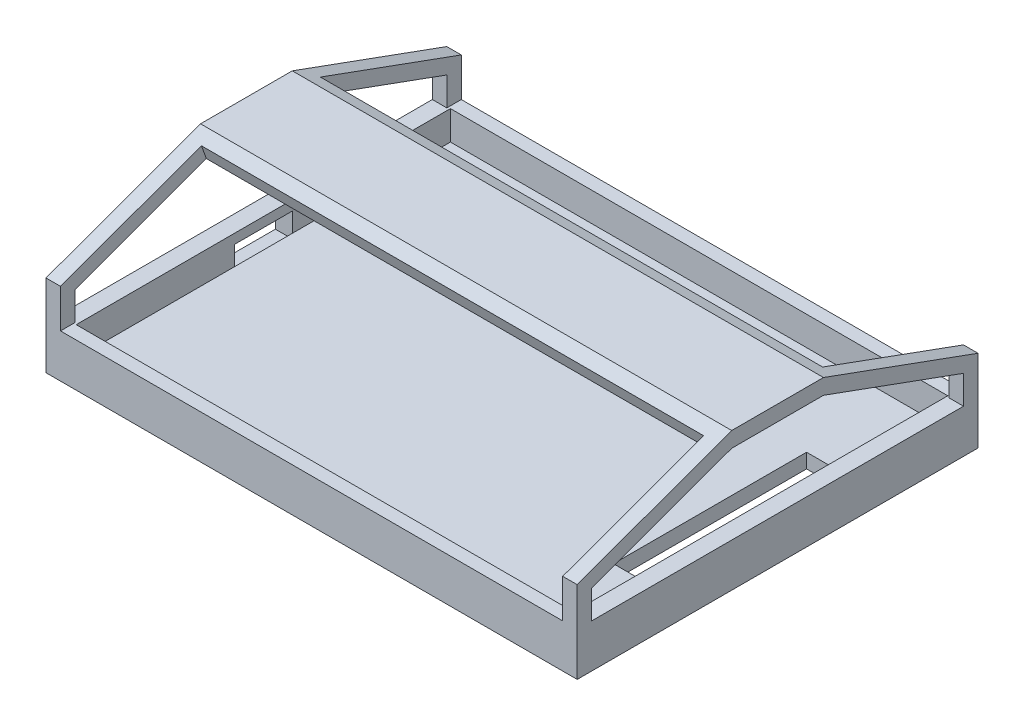
SolidWorks part; units mm, degrees
ref_plane "Front Plane" through (0, 0, 0) normal (0, 0, 1) x (1, 0, 0)
ref_plane "Top Plane" through (0, 0, 0) normal (0, 1, 0) x (1, 0, 0)
ref_plane "Right Plane" through (0, 0, 0) normal (1, 0, 0) x (0, 0, -1)
sketch "Sketch2" plane through (0, 0, 0) normal (0, 1, 0) x (1, 0, 0)
  line L0 (-55, 41.5) -> (55, -41.5) construction
  line L1 (-55, 41.5) -> (55, 41.5)
  line L2 (-55, 41.5) -> (-55, -41.5)
  line L3 (-55, -41.5) -> (55, -41.5)
  line L4 (55, 41.5) -> (55, -41.5)
  line L5 (-55, -41.5) -> (55, 41.5) construction
  line L6 (-55, 0) -> (55, 0) construction
  line L21 (51, 20) -> (41, 20)
  line L22 (41, 20) -> (41, -20)
  line L23 (41, -20) -> (51, -20)
  line L24 (51, -20) -> (51, 20)
  point P8 (0, 0)
  point P9 (0, 0)
  point P13 (0, 0)
  point P14 (0, 0)
  point P15 (41, 0)
  dimension "D1" = 110
  dimension "D2" = 83
  dimension "D3" = 40
  dimension "D4" = 10
  dimension "D5" = 4
extrude "Boss-Extrude1" add sketch "Sketch2" along normal blind 9
sketch "Sketch4" plane through (0, 9, 0) normal (0, 1, 0) x (1, 0, 0)
  line L1 (-51.5, 38.75) -> (51.5, 38.75)
  line L2 (-51.5, 38.75) -> (-51.5, -38.75)
  line L3 (-51.5, -38.75) -> (51.5, -38.75)
  line L4 (51.5, 38.75) -> (51.5, -38.75)
  line L5 (-51.5, 38.75) -> (51.5, -38.75) construction
  line L6 (-51.5, -38.75) -> (51.5, 38.75) construction
  line L7 (-55, 41.5) -> (55, -41.5) construction
  point P0 (0, 0)
  point P13 (0, 0)
  dimension "D1" = 103
  dimension "D2" = 77.5
extrude "Cut-Extrude1" cut sketch "Sketch4" against normal blind 6
sketch "Sketch5" plane through (-55, 0, 0) normal (-1, 0, 0) x (0, 0, 1)
  line L1 (38.5, 9) -> (41.5, 9)
  line L13 (-41.5, 9) -> (-41.5, 17)
  line L14 (-41.5, 17) -> (-9.5, 28.647)
  line L15 (-9.5, 28.647) -> (9.5, 28.647)
  line L16 (9.5, 28.647) -> (41.5, 17)
  line L17 (41.5, 17) -> (41.5, 9)
  line L18 (-41.5, 9) -> (41.5, 9) construction
  line L19 (-41.5, 17) -> (41.5, 17) construction
  line L20 (-9.5, 28.647) -> (-9.5, 17) construction
  line L21 (9.5, 28.647) -> (9.5, 17) construction
  line L22 (-38.5, 9) -> (-38.5, 14.8994)
  line L23 (-38.5, 14.8994) -> (-9.5, 25.4545)
  line L24 (-9.5, 25.4545) -> (9.5, 25.4545)
  line L25 (9.5, 25.4545) -> (38.5, 14.8994)
  line L26 (38.5, 14.8994) -> (38.5, 9)
  line L27 (-38.5, 9) -> (-41.5, 9)
  point P15 (-25.5, 22.8235)
  dimension "D1" = 20
  dimension "D2" = 20
  dimension "D3" = 32
  dimension "D4" = 8
  dimension "D5" = 3
  dimension "D6" = 3
  dimension "D7" = 3
extrude "Boss-Extrude2" add sketch "Sketch5" against normal blind 110
sketch "Sketch6" plane through (0, 28.3492, 10.3183) normal (0, 0.9397, 0.342) x (1, 0, 0)
  line L0 (55, 0.8708) -> (-55, 0.8708) construction
  line L1 (55, -33.1829) -> (55, 0.8708) construction
  line L2 (-55, -33.1829) -> (-55, 0.8708) construction
  line L3 (-52, -2.1292) -> (52, -2.1292)
  line L4 (-52, -2.1292) -> (-52, -30.1829)
  line L5 (-52, -30.1829) -> (52, -30.1829)
  line L6 (52, -2.1292) -> (52, -30.1829)
  line L7 (-52, -2.1292) -> (52, -30.1829) construction
  line L8 (-52, -30.1829) -> (52, -2.1292) construction
  line L10 (55, -33.1829) -> (-55, -33.1829) construction
  point P4 (0, -16.1561)
  dimension "D1" = 3
  dimension "D2" = 3
  dimension "D3" = 3
  dimension "D4" = 3
extrude "Cut-Extrude3" cut sketch "Sketch6" against normal blind 3
sketch "Sketch7" plane through (0, 28.3492, -10.3183) normal (0, 0.9397, -0.342) x (1, 0, 0)
  line L0 (55, -0.8708) -> (-55, -0.8708) construction
  line L1 (52, 2.1292) -> (-52, 2.1292)
  line L2 (52, 2.1292) -> (52, 32.4711)
  line L3 (52, 32.4711) -> (-52, 32.4711)
  line L4 (-52, 2.1292) -> (-52, 32.4711)
  line L5 (52, 2.1292) -> (-52, 32.4711) construction
  line L6 (52, 32.4711) -> (-52, 2.1292) construction
  line L7 (55, -0.8708) -> (55, 33.1829) construction
  line L8 (-55, -0.8708) -> (-55, 33.1829) construction
  point P0 (0, 17.3001)
  dimension "D1" = 3
  dimension "D2" = 3
  dimension "D3" = 3
extrude "Cut-Extrude4" cut sketch "Sketch7" against normal up to next
sketch "Sketch8" plane through (0, 0, -41.5) normal (0, 0, -1) x (-1, 0, 0)
  line L0 (-52, 21.221) -> (-52, 9)
  line L2 (-52, 9) -> (52, 9)
  line L3 (52, 9) -> (52, 21.221)
  line L5 (52, 21.221) -> (-52, 21.221)
  point P1 (0, 0)
  point P3 (0, 0)
  point P4 (0, 0)
  point P5 (0, 0)
  point P8 (0, 0)
  point P9 (0, 0)
  point P10 (0, 0)
  point P12 (0, 0)
  point P13 (0, 0)
  point P15 (0, 0)
  point P16 (0, 0)
  point P17 (0, 0)
extrude "Cut-Extrude5" cut sketch "Sketch8" against normal through all
sketch "Sketch10" plane through (-55, 0, 0) normal (-1, 0, 0) x (0, 0, 1)
  line L1 (-6, 7) -> (6, 7)
  line L2 (-6, 7) -> (-6, 2)
  line L3 (-6, 2) -> (6, 2)
  line L4 (6, 7) -> (6, 2)
  line L5 (-6, 7) -> (6, 2) construction
  line L6 (-6, 2) -> (6, 7) construction
  line L7 (-38.5, 9) -> (-41.5, 9) construction
  line L8 (-41.5, 17) -> (-41.5, 0) construction
  line L9 (-41.5, 9) -> (-41.5, 0) construction
  point P0 (0, 4.5)
  point P5 (-41.5, 4.5)
  point P9 (0, 2)
  point P16 (-6, 4.5)
  dimension "D2" = 12
  dimension "D3" = 5
extrude "Cut-Extrude7" cut sketch "Sketch10" against normal up to vertex (3.5 mm away) up to point (-51.5, 9, -38.75)
